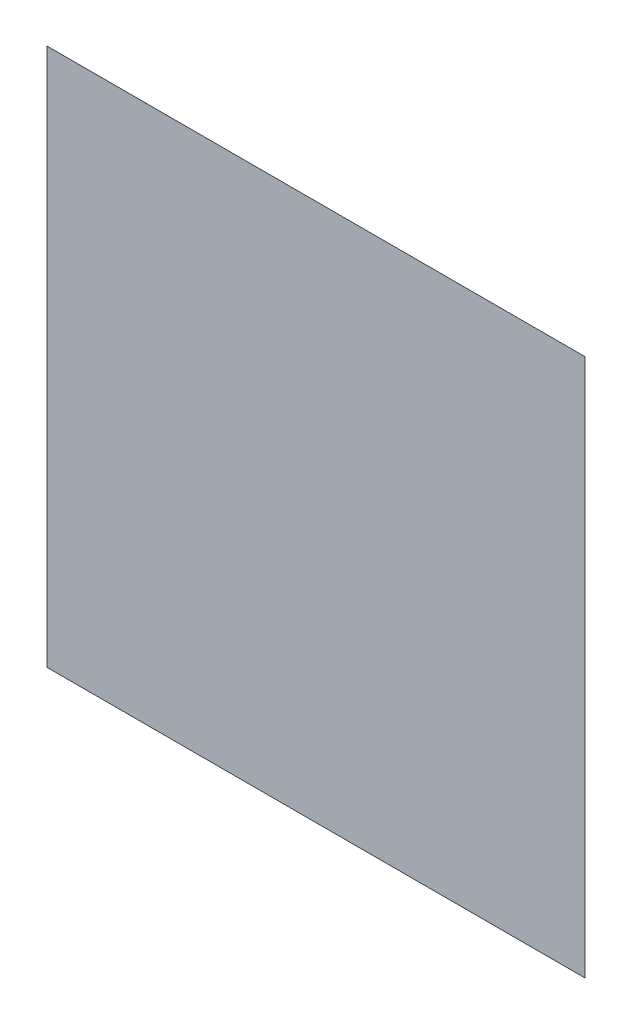
SolidWorks part; units mm, degrees
ref_plane "Plan de face" through (0, 0, 0) normal (0, 0, 1) x (1, 0, 0)
ref_plane "Plan de dessus" through (0, 0, 0) normal (0, 1, 0) x (1, 0, 0)
ref_plane "Plan de droite" through (0, 0, 0) normal (1, 0, 0) x (0, 0, -1)
sketch "Esquisse1" plane through (0, 0, 0) normal (0, 0, 1) x (1, 0, 0)
  line L1 (-5000, -5000) -> (5000, -5000)
  line L2 (-5000, -5000) -> (-5000, 5000)
  line L3 (-5000, 5000) -> (5000, 5000)
  line L4 (5000, -5000) -> (5000, 5000)
  point P4 (0, 0)
  point P5 (0, -5000)
  point P6 (5000, 0)
  dimension "D1" = 10000
  dimension "D2" = 10000
  dimension "D3" = 0
  dimension "D4" = 0
extrude "Boss.-Extru.1" add sketch "Esquisse1" along normal blind 0.025 and the other way blind 0.025
